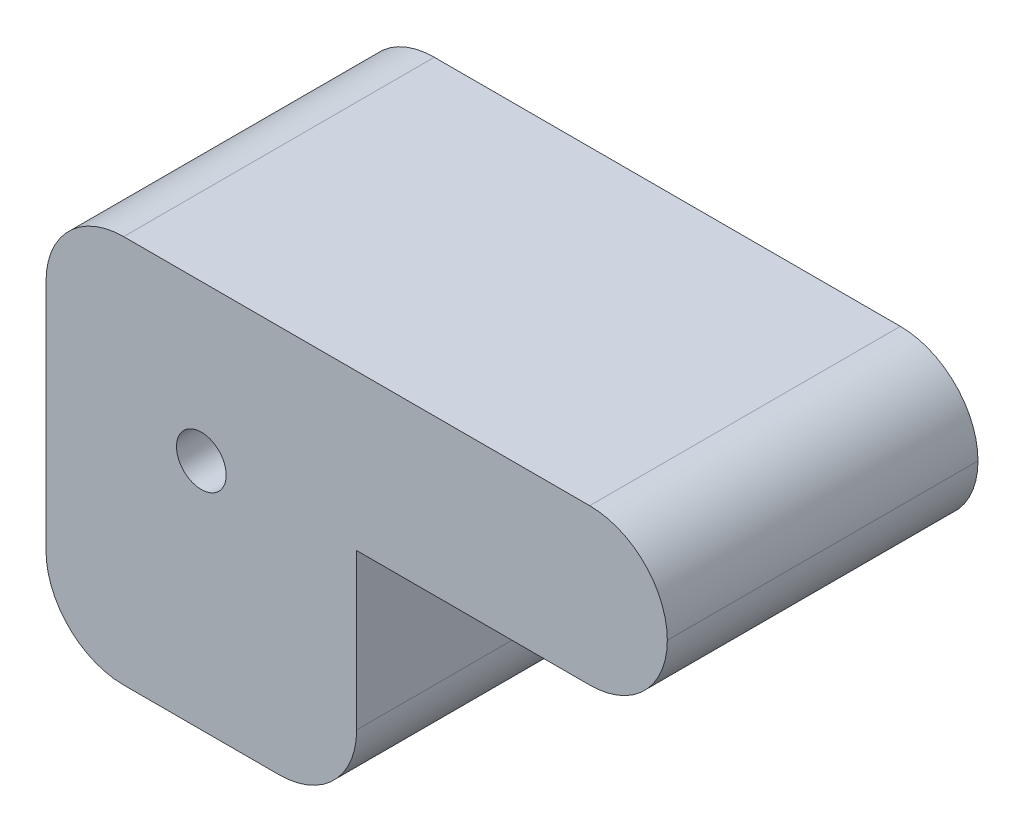
SolidWorks part; units mm, degrees
material "ABS"
ref_plane "前视基准面" through (0, 0, 0) normal (0, 0, 1) x (1, 0, 0)
ref_plane "上视基准面" through (0, 0, 0) normal (0, 1, 0) x (1, 0, 0)
ref_plane "右视基准面" through (0, 0, 0) normal (1, 0, 0) x (0, 0, -1)
other "Configuration Table"
sketch "草图1" plane through (0, 0, 0) normal (0, 0, 1) x (1, 0, 0)
  line L1 (0, 0) -> (-40, 0)
  line L2 (0, 0) -> (0, 10)
  line L3 (0, 10) -> (-40, 10)
  line L4 (-40, 0) -> (-40, 10)
  dimension "D1" = 10
  dimension "D2" = 40
extrude "凸台-拉伸1" add sketch "草图1" along normal blind 20
sketch "草图2" plane through (0, 0, 20) normal (0, 0, 1) x (1, 0, 0)
  line L1 (-40, 10) -> (-20, 10)
  line L2 (-40, 10) -> (-40, -15)
  line L3 (-40, -15) -> (-20, -15)
  line L4 (-20, 10) -> (-20, -15)
  dimension "D1" = 20
  dimension "D2" = 25
extrude "凸台-拉伸2" add sketch "草图2" against normal blind 20
fillet "圆角1" radius 5 5 edges at (0, 10, 10) (0, 0, 10) (-20, -15, 10) (-40, -15, 10) (-40, 10, 10)
sketch "草图3" plane through (0, 0, 20) normal (0, 0, 1) x (1, 0, 0)
  line L0 (-30, -15) -> (-30, 10) construction
  line L1 (-35, -15) -> (-25, -15) construction
  line L2 (-5, 10) -> (-35, 10) construction
  circle A0 centre (-30, 0) radius 1.6
  dimension "D1" = 3.2
  dimension "D2" = 10
extrude "切除-拉伸1" cut sketch "草图3" against normal through all
